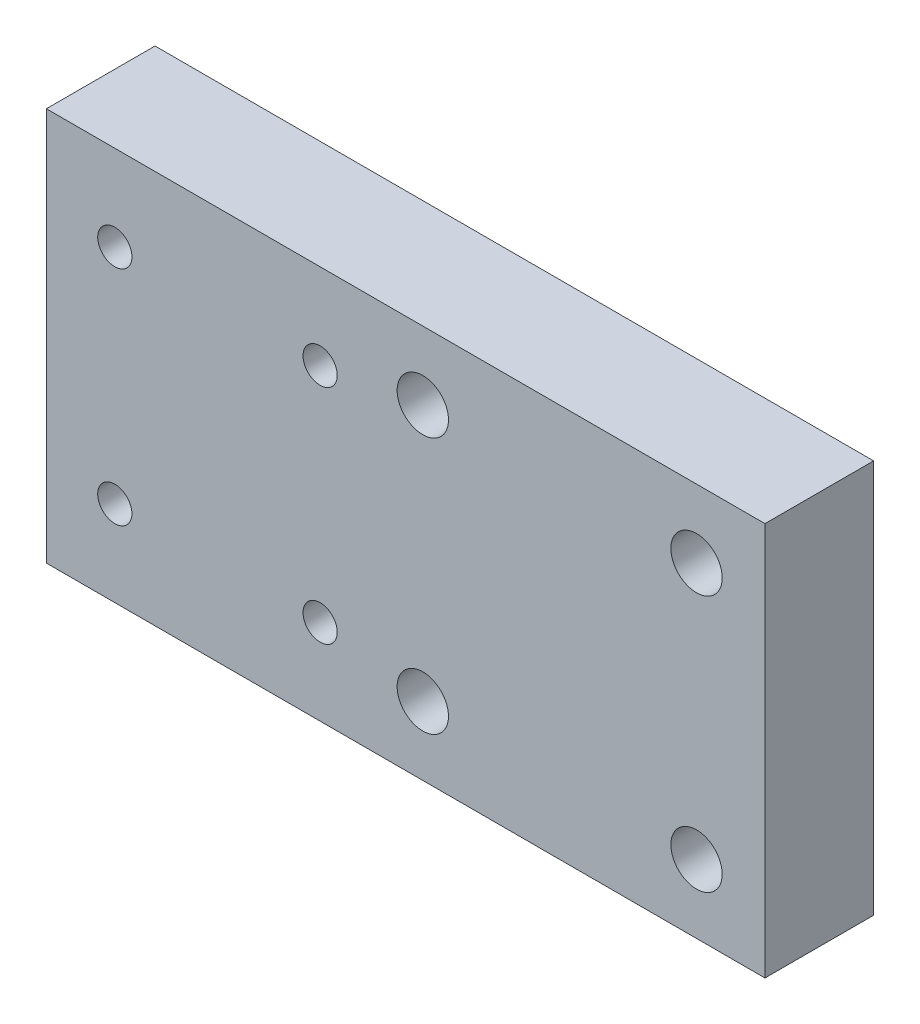
SolidWorks part; units mm, degrees
ref_plane "Front Plane" through (0, 0, 0) normal (0, 0, 1) x (1, 0, 0)
ref_plane "Top Plane" through (0, 0, 0) normal (0, 1, 0) x (1, 0, 0)
ref_plane "Right Plane" through (0, 0, 0) normal (1, 0, 0) x (0, 0, -1)
sketch "Sketch1" plane through (0, 0, 0) normal (0, 0, 1) x (1, 0, 0)
  line L0 (-8, 7.5) -> (8, 7.5) construction
  line L5 (-26, 6.5) -> (-14, 6.5) construction
  line L7 (-8, -7.5) -> (8, -7.5) construction
  line L8 (-8, -7.5) -> (-8, 7.5) construction
  line L9 (-8, 7.5) -> (8, 7.5) construction
  line L10 (8, -7.5) -> (8, 7.5) construction
  line L11 (-8, -7.5) -> (8, 7.5) construction
  line L12 (-8, 7.5) -> (8, -7.5) construction
  line L13 (-8, 7.5) -> (-8, -7.5) construction
  line L14 (-26, -6.5) -> (-14, -6.5) construction
  line L15 (-26, -6.5) -> (-26, 6.5) construction
  line L16 (-26, 6.5) -> (-14, 6.5) construction
  line L17 (-14, -6.5) -> (-14, 6.5) construction
  line L18 (-26, -6.5) -> (-14, 6.5) construction
  line L19 (-26, 6.5) -> (-14, -6.5) construction
  line L20 (0, 0) -> (-20, 0) construction
  line L22 (-30, -11.5) -> (12, -11.5)
  line L23 (-30, -11.5) -> (-30, 11.5)
  line L24 (-30, 11.5) -> (12, 11.5)
  line L25 (12, -11.5) -> (12, 11.5)
  line L26 (-30, -11.5) -> (12, 11.5) construction
  line L27 (-30, 11.5) -> (12, -11.5) construction
  line L28 (-11.5, -15) -> (-28.5, -15) construction
  line L29 (-11.5, -15) -> (-11.5, 15) construction
  line L30 (-11.5, 15) -> (-28.5, 15) construction
  line L31 (-28.5, -15) -> (-28.5, 15) construction
  line L32 (-11.5, -15) -> (-28.5, 15) construction
  line L33 (-11.5, 15) -> (-28.5, -15) construction
  circle A0 centre (-8, 7.5) radius 1.5
  circle A2 centre (8, 7.5) radius 1.5
  circle A3 centre (8, -7.5) radius 1.5
  circle A4 centre (-8, -7.5) radius 1.5
  circle A5 centre (-26, 6.5) radius 1
  circle A6 centre (-14, 6.5) radius 1
  circle A7 centre (-14, -6.5) radius 1
  circle A8 centre (-26, -6.5) radius 1
  circle A9 centre (-8, 7.5) radius 2.9 construction
  point P0 (0, 0)
  point P1 (-20, 0)
  point P4 (-9, 0)
  point P6 (0, 0)
  point P42 (12, 11.5)
  point P43 (12, -11.5)
  point P44 (0, 0)
  dimension "D5" = 3
  dimension "D6" = 2
  dimension "D18" = 5.8
  dimension "D1" = 15
  dimension "D2" = 16
  dimension "D3" = 13
  dimension "D4" = 12
  dimension "D9" = 16
  dimension "D10" = 15
  dimension "D13" = 12
  dimension "D14" = 20
  dimension "D15" = 23
  dimension "D16" = 4
  dimension "D17" = 4
  dimension "D19" = 17
  dimension "D20" = 30
  dimension "D7" = 2
  dimension "D8" = 2
  dimension "D11" = 2
  dimension "D12" = 2
extrude "Boss-Extrude1" add sketch "Sketch1" along normal blind 6.35
